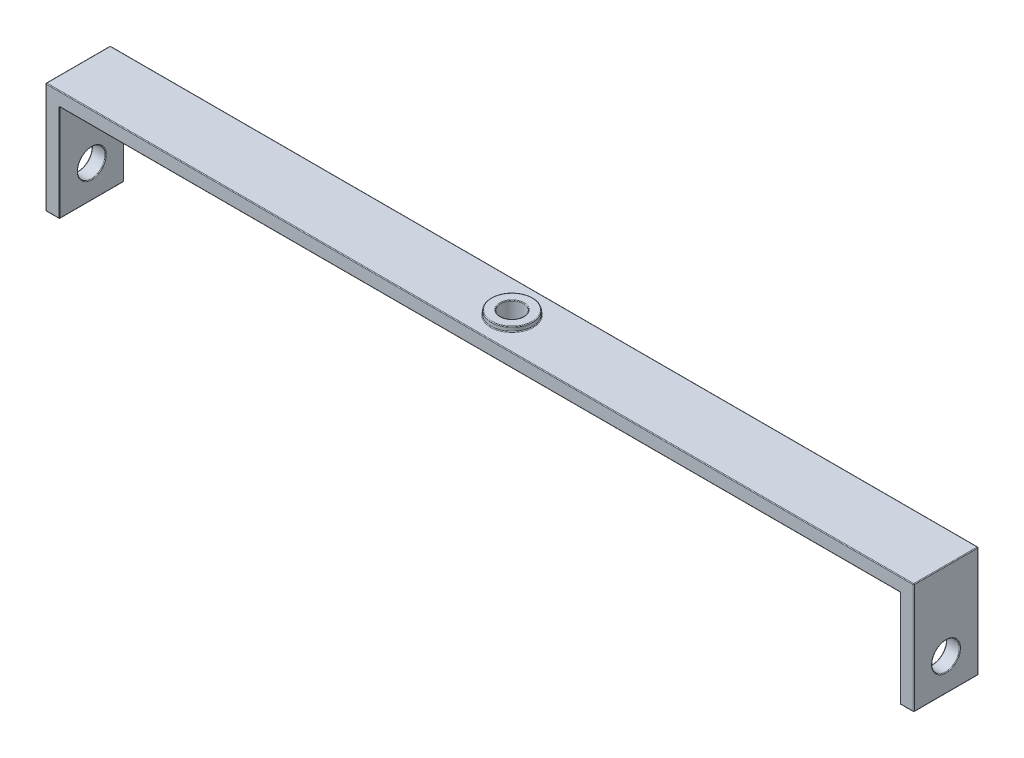
SolidWorks part; units mm, degrees
ref_plane "Front Plane" through (0, 0, 0) normal (0, 0, 1) x (1, 0, 0)
ref_plane "Top Plane" through (0, 0, 0) normal (0, 1, 0) x (1, 0, 0)
ref_plane "Right Plane" through (0, 0, 0) normal (1, 0, 0) x (0, 0, -1)
sketch "Sketch1" plane through (0, 0, 0) normal (0, 0, 1) x (1, 0, 0)
  line L0 (-47, 0) -> (47, 0)
  line L1 (47, 0) -> (47, -12)
  line L2 (-47, 0) -> (-47, -12)
  line L3 (-45.5, -1.5) -> (-45.5, -12)
  line L4 (-45.5, -1.5) -> (45.5, -1.5)
  line L5 (45.5, -1.5) -> (45.5, -12)
  line L6 (-47, -12) -> (-45.5, -12)
  line L7 (45.5, -12) -> (47, -12)
  dimension "D1" = 94
  dimension "D2" = 12
  dimension "D3" = 12
  dimension "D4" = 1.5
extrude "Boss-Extrude1" add sketch "Sketch1" along normal blind 3.5 and the other way blind 3.5
sketch "Sketch2" plane through (0, 0, 0) normal (0, 1, 0) x (1, 0, 0)
  circle A0 centre (0, 0) radius 1.25
  dimension "D1" = 2.5
extrude "Cut-Extrude1" cut sketch "Sketch2" against normal through all both and the other way through all
sketch "Sketch3" plane through (0, 0, 0) normal (0, 1, 0) x (1, 0, 0)
  line L4 (-47, 3.5) -> (-47, -3.5)
  line L5 (-47, -3.5) -> (47, -3.5)
  line L6 (47, -3.5) -> (47, 3.5)
  line L7 (47, 3.5) -> (-47, 3.5)
  line L8 (-47, 3.5) -> (-47, -3.5)
  line L9 (-47, -3.5) -> (47, -3.5)
  line L10 (47, -3.5) -> (47, 3.5)
  line L11 (47, 3.5) -> (-47, 3.5)
  circle A0 centre (0, 0) radius 1.25 construction
  circle A1 centre (0, 0) radius 1.25
  circle A2 centre (0, 0) radius 2.25
  circle M5 centre (0, 0) radius 1.25
  dimension "D1" = 0
  dimension "D2" = 1
extrude "Boss-Extrude2" add sketch "Sketch3" along normal blind 0.5 contours A2 M5 region at (-2.1864, 0, 0)
sketch "Sketch4" plane through (0, 0, 0) normal (1, 0, 0) x (0, 0, -1)
  line L0 (0, 0) -> (0, -8.5) construction
  circle A0 centre (0, -8.5) radius 1.5
  dimension "D1" = 3
  dimension "D2" = 8.5
extrude "Cut-Extrude2" cut sketch "Sketch4" against normal through all both and the other way through all
fillet "Fillet1" radius 0.075 32 edges at (47, -8.5, -1.5) (-47, -8.5, -1.5) (-45.5, -8.5, -1.5) (45.5, -8.5, 1.5) (0, 0, 2.25) (0, 0.5, 1.25) (0, 0.5, 2.25) (0, -1.5, -1.25) (-47, -6, 3.5) (-46.25, -12, 3.5) (-45.5, -6.75, 3.5) (0, -1.5, 3.5) (45.5, -6.75, 3.5) (46.25, -12, 3.5) (47, -6, 3.5) (-47, -6, -3.5) (-46.25, -12, -3.5) (-45.5, -6.75, -3.5) (0, -1.5, -3.5) (45.5, -6.75, -3.5) (46.25, -12, -3.5) (47, -6, -3.5) (0, 0, -3.5) (-47, -12, 0) (-45.5, -12, 0) (-45.5, -1.5, 0) (45.5, -1.5, 0) (45.5, -12, 0) (47, -12, 0) (47, 0, 0) (-47, 0, 0) (0, 0, 3.5)
